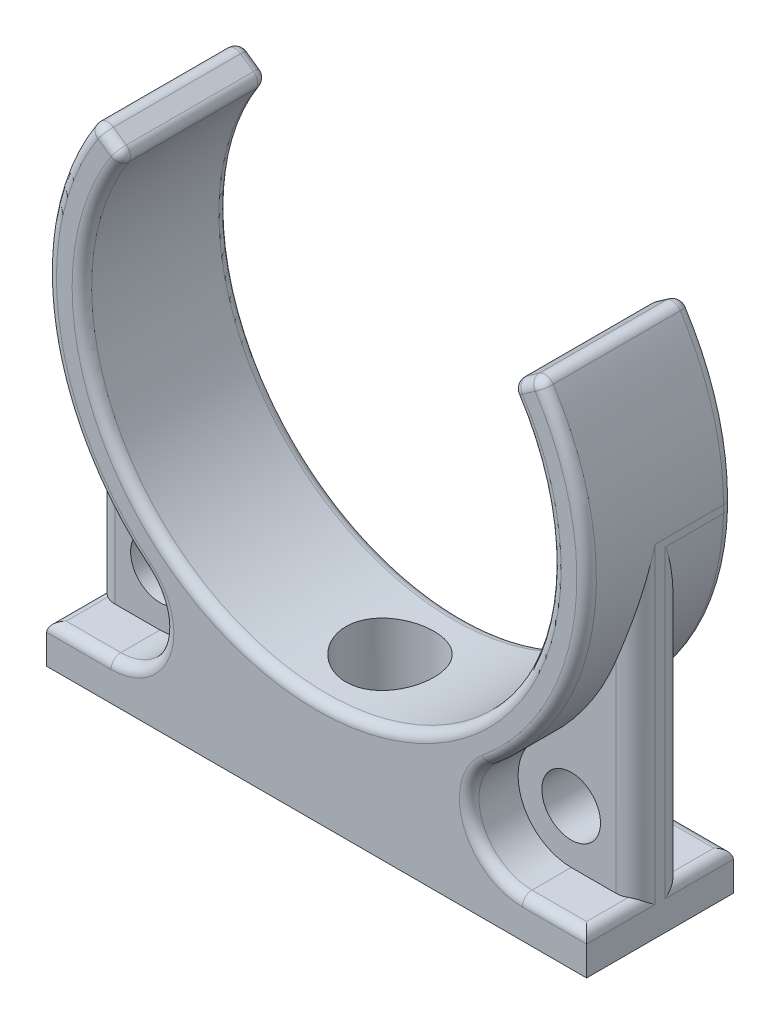
SolidWorks part; units mm, degrees
ref_plane "Front Plane" through (0, 0, 0) normal (0, 0, 1) x (1, 0, 0)
ref_plane "Top Plane" through (0, 0, 0) normal (0, 1, 0) x (1, 0, 0)
ref_plane "Right Plane" through (0, 0, 0) normal (1, 0, 0) x (0, 0, -1)
sketch "Sketch1" plane through (0, 0, 0) normal (0, 0, 1) x (1, 0, 0)
  line L0 (0, 0) -> (0, 29.845) construction
  line L1 (0, 0) -> (24.9678, 17.4826) construction
  line L2 (0, 0) -> (-24.9678, 17.4826) construction
  line L3 (-24.9678, 17.4826) -> (-28.7129, 20.105)
  line L4 (24.9678, 17.4826) -> (28.7129, 20.105)
  line L5 (0, -29.972) -> (0, -44.323) construction
  line L6 (-35.052, -44.323) -> (35.052, -44.323)
  line L7 (-35.052, -44.323) -> (-35.052, 0)
  line L8 (35.052, -44.323) -> (35.052, 0)
  arc A0 (-24.9678, 17.4826) -> (24.9678, 17.4826) centre (0, 0) ccw
  arc A1 (-28.7129, 20.105) -> (-35.052, 0) centre (0, 0) ccw
  arc A2 (35.052, 0) -> (28.7129, 20.105) centre (0, 0) ccw
  point P12 (0, -44.323)
  dimension "D1" = 60.96
  dimension "D3" = 70.104
  dimension "D2" = 110
  dimension "D4" = 14.351
  dimension "D5" = 44.323
extrude "Boss-Extrude1" add sketch "Sketch1" along normal blind 19.05
sketch "Sketch2" plane through (0, -44.323, 0) normal (0, -1, 0) x (1, 0, 0)
  line L0 (-35.052, 19.05) -> (35.052, 0) construction
  circle A0 centre (0, 9.525) radius 5.715
  dimension "D1" = 11.43
extrude "Cut-Extrude1" cut sketch "Sketch2" against normal blind 19.05 from offset 5.08 offset against normal yes
sketch "Sketch3" plane through (0, -44.323, 0) normal (0, -1, 0) x (1, 0, 0)
  line L0 (-35.052, 19.05) -> (35.052, 0) construction
  circle A0 centre (0, 9.525) radius 2.54
  dimension "D1" = 5.08
extrude "Cut-Extrude2" cut sketch "Sketch3" against normal blind 19.05
sketch "Sketch4" plane through (0, 0, 19.05) normal (0, 0, 1) x (1, 0, 0)
  line L0 (-35.052, 0) -> (-35.052, -44.323) construction
  line L1 (-35.052, -39.243) -> (35.052, -39.243) construction
  line L2 (35.052, -44.323) -> (35.052, 0) construction
  line L3 (-35.052, -39.243) -> (-26.701, -39.243)
  line L4 (0, -35.052) -> (0, -44.323) construction
  line L5 (26.701, -39.243) -> (35.052, -39.243)
  line L6 (-35.052, 0) -> (-35.052, -39.243)
  line L7 (35.052, 0) -> (35.052, -39.243)
  arc A0 (-35.052, 0) -> (-22.3128, -27.0329) centre (0, 0) ccw
  arc A1 (35.052, 0) -> (28.7129, 20.105) centre (0, 0) ccw construction
  arc A2 (-26.701, -39.243) -> (-22.3128, -27.0329) centre (-26.701, -32.3494) ccw
  arc A3 (26.701, -39.243) -> (22.3128, -27.0329) centre (26.701, -32.3494) cw
  arc A4 (22.3128, -27.0329) -> (35.052, 0) centre (0, 0) ccw
  point P8 (-35.052, -39.243)
  point P18 (-26.701, -39.243)
  dimension "D2" = 6.8936
  dimension "D1" = 5.08
extrude "Cut-Extrude3" cut sketch "Sketch4" against normal blind 6.35
sketch "Sketch5" plane through (0, 0, 0) normal (0, 0, -1) x (-1, 0, 0)
  line L0 (0, -30.48) -> (0, -44.323) construction
  line L1 (35.052, -44.323) -> (-35.052, -44.323) construction
  line L2 (-35.0655, -39.243) -> (35.0655, -39.243) construction
  line L3 (-35.0655, -39.243) -> (-26.7223, -39.243)
  line L4 (0, -35.052) -> (0, -39.243) construction
  line L5 (26.7223, -39.243) -> (35.0655, -39.243)
  line L6 (-35.0655, 0) -> (-35.0655, -39.243)
  line L7 (35.0655, 0) -> (35.0655, -39.243)
  arc A0 (-5.715, -29.9394) -> (5.715, -29.9394) centre (0, 0) ccw construction
  arc A1 (-35.0655, 0) -> (-22.332, -27.0347) centre (0, 0) ccw
  arc A2 (-26.7223, -39.243) -> (-22.332, -27.0347) centre (-26.7223, -32.3494) ccw
  arc A3 (26.7223, -39.243) -> (22.332, -27.0347) centre (26.7223, -32.3494) cw
  arc A4 (22.332, -27.0347) -> (35.0655, 0) centre (0, 0) ccw
  arc A5 (-28.7129, 20.105) -> (-35.052, 0) centre (0, 0) ccw construction
  point P10 (-35.0655, -39.243)
  point P15 (-26.7223, -39.243)
  dimension "D1" = 6.8936
  dimension "D3" = 35.0655
  dimension "D2" = 5.08
extrude "Cut-Extrude4" cut sketch "Sketch5" against normal blind 6.35
sketch "Sketch6" plane through (0, 0, 12.7) normal (0, 0, 1) x (1, 0, 0)
  line L0 (0, -30.48) -> (0, -44.323) construction
  line L1 (-35.052, -44.323) -> (35.052, -44.323) construction
  line L2 (-20.2137, -34.6809) -> (-26.701, -32.3494) construction
  line L3 (-26.701, -32.3494) -> (-35.052, -32.3494) construction
  line L4 (-35.052, 0) -> (-35.052, -39.243) construction
  arc A0 (-24.9678, 17.4826) -> (24.9678, 17.4826) centre (0, 0) ccw construction
  arc A1 (-26.701, -39.243) -> (-22.3128, -27.0329) centre (-26.701, -32.3494) ccw construction
  circle A2 centre (-26.701, -32.3494) radius 3.81
  circle A3 centre (26.701, -32.3494) radius 3.81
  dimension "D1" = 7.62
extrude "Cut-Extrude5" cut sketch "Sketch6" against normal blind 6.35
fillet "Fillet3" radius 1.27 30 edges at (-30.8871, -39.243, 0) (-20.2354, -34.6822, 0) (30.8871, -39.243, 0) (20.2354, -34.6822, 0) (-30.8765, -39.243, 19.05) (-20.2137, -34.6809, 19.05) (-35.052, -0.4873, 0) (30.8765, -39.243, 19.05) (20.2137, -34.6809, 19.05) (35.052, -0.4873, 0) (-24.9678, 17.4826, 9.525) (-28.7129, 20.105, 9.525) (28.7129, 20.105, 9.525) (24.9678, 17.4826, 9.525) (35.052, -39.243, 15.875) (35.052, -39.243, 3.175) (-35.052, -39.243, 15.875) (-35.052, -39.243, 3.175) (-31.5121, -15.3811, 0) (31.5121, -15.3811, 0) (-34.7333, -4.7159, 19.05) (-33.4297, 10.5403, 0) (34.7333, -4.7159, 19.05) (33.4297, 10.5403, 0) (0, -30.48, 0) (0, -30.48, 19.05) (-26.8403, 18.7938, 19.05) (-26.8403, 18.7938, 0) (26.8403, 18.7938, 19.05) (26.8403, 18.7938, 0)
fillet "Fillet4" radius 2.54 4 edges at (-35.052, -20.2565, 12.7) (-35.052, -20.7438, 6.35) (35.052, -20.7438, 6.35) (35.052, -20.2565, 12.7)
